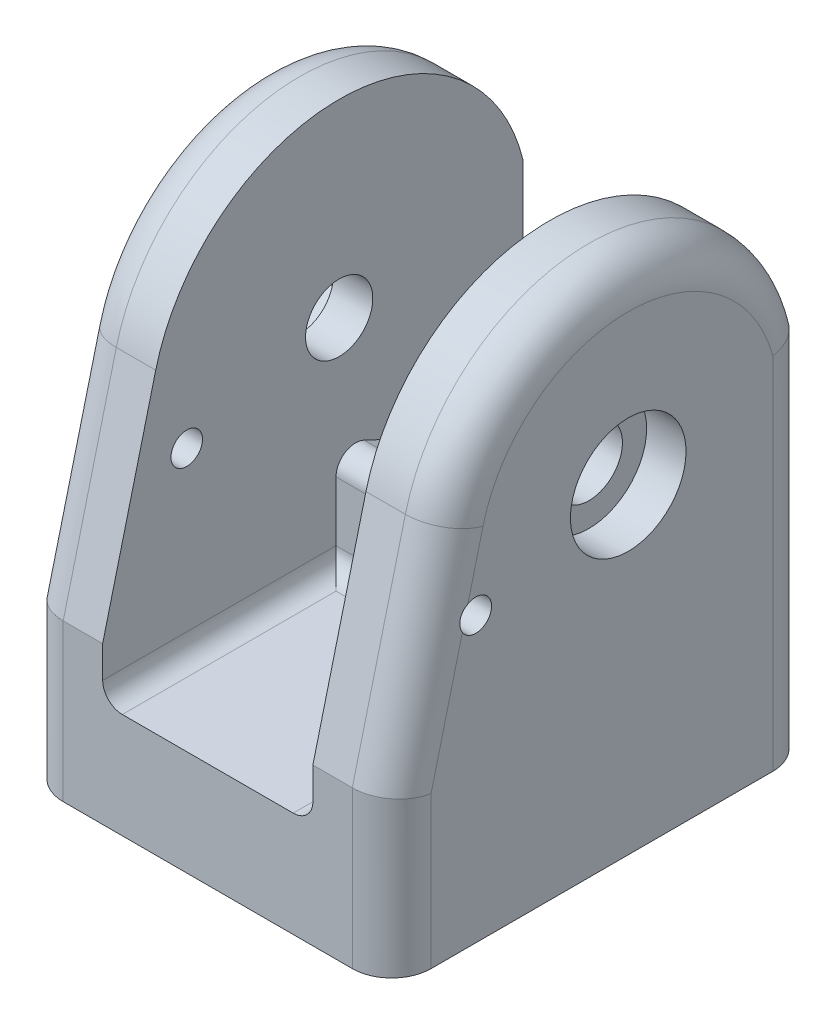
SolidWorks part; units mm, degrees
ref_plane "Front Plane" through (0, 0, 0) normal (0, 0, 1) x (1, 0, 0)
ref_plane "Top Plane" through (0, 0, 0) normal (0, 1, 0) x (1, 0, 0)
ref_plane "Right Plane" through (0, 0, 0) normal (1, 0, 0) x (0, 0, -1)
sketch "Sketch2" plane through (0, 0, 0) normal (0, 1, 0) x (1, 0, 0)
  line L0 (5, 10) -> (8.75, 10)
  line L1 (-8.75, -10) -> (8.75, -10)
  line L2 (-8.75, -10) -> (-8.75, 10)
  line L3 (-8.75, 10) -> (-5, 10)
  line L4 (8.75, -10) -> (8.75, 10)
  line L5 (-8.75, -10) -> (8.75, 10) construction
  line L6 (-8.75, 10) -> (8.75, -10) construction
  line L8 (-5, 10) -> (-5, 5)
  line L9 (-5, 5) -> (5, 5)
  line L10 (5, 10) -> (5, 5)
  point P0 (0, 0)
  point P6 (0, 0)
  point P8 (0, 0)
  point P15 (-5, 5)
  dimension "D1" = 17.5
  dimension "D2" = 20
  dimension "D3" = 3.75
  dimension "D4" = 5
extrude "Boss-Extrude1" add sketch "Sketch2" along normal blind 25
sketch "Sketch3" plane through (0, 25, 0) normal (0, 1, 0) x (1, 0, 0)
  line L0 (-8.75, -10) -> (8.75, -10) construction
  line L1 (-5, 10) -> (5, 10)
  line L2 (-5, 10) -> (-5, -10)
  line L3 (-5, -10) -> (5, -10)
  line L4 (5, 10) -> (5, -10)
  line L5 (5, 10) -> (5, 5) construction
extrude "Cut-Extrude1" cut sketch "Sketch3" against normal blind 20
sketch "Sketch4" plane through (8.75, 0, 0) normal (1, 0, 0) x (0, 0, -1)
  line L0 (10, 25) -> (10, 0) construction
  line L1 (-10, 25) -> (10, 25) construction
  line L2 (10, 17.3565) -> (10, 0)
  line L3 (10, 0) -> (-10, 0)
  line L4 (-10, 0) -> (-10, 7.4522)
  line L6 (-10, 7.4522) -> (-7.4764, 17.4522)
  line L7 (-10, 25) -> (-10, 0) construction
  circle A0 centre (1.25, 15.25) radius 1.6
  arc A1 (10, 17.3565) -> (-7.4764, 17.4522) centre (1.25, 15.25) ccw
  circle A2 centre (-6, 13.5) radius 0.75
  point P2 (0, 0)
  dimension "D1" = 8.75
  dimension "D4" = 3.2
  dimension "D7" = 9
  dimension "D6" = 1.75
  dimension "D8" = 1.5
  dimension "D2" = 9.75
  dimension "D3" = 10
  dimension "D5" = 4
extrude "Cut-Extrude2" cut sketch "Sketch4" against normal through all flip side to cut
fillet "Fillet1" radius 1.875 8 edges at (-8.75, 12.4522, 8.7382) (8.75, 12.4522, 8.7382) (-8.75, 8.6783, -10) (8.75, 8.6783, -10) (-8.75, 3.7261, 10) (8.75, 3.7261, 10) (-8.75, 24.2499, -1.2993) (8.75, 24.2499, -1.2993)
sketch "Sketch7" plane through (8.75, 0, 0) normal (1, 0, 0) x (0, 0, -1)
  line L1 (-10, 0) -> (10, 0)
  line L2 (-10, 0) -> (-10, 25)
  line L3 (-10, 25) -> (10, 25)
  line L4 (10, 0) -> (10, 25)
  dimension "D1" = 25
  dimension "D2" = 20
extrude "Cut-Extrude4" cut sketch "Sketch7" against normal blind 8.75
sketch "Sketch8" plane through (-5, 0, 0) normal (1, 0, 0) x (0, 0, -1)
  line L0 (5, 5) -> (5, 8.4)
  line L2 (5, 8.4) -> (1.1, 10.25)
  line L3 (1.1, 10.25) -> (1.1, 5)
  line L4 (5, 5) -> (-10, 5) construction
  line L5 (1.1, 5) -> (5, 5)
  line L7 (5, 5) -> (5, 0) construction
  point P10 (0, 0)
  point P13 (0, 0)
  point P14 (0, 0)
  dimension "D1" = 3.4
  dimension "D2" = 5.25
  dimension "D3" = 3.9
extrude "Boss-Extrude3" add sketch "Sketch8" along normal up to surface (5 mm away) up to face at (0, 2.5, 2.5)
fillet "Fillet2" radius 0.9375 4 edges at (-2.5, 8.4, -5) (-2.5, 10.25, -1.1) (-2.5, 5, -1.1) (-5, 5, 4.45)
mirror "Mirror2" about plane through (0, 0, 0) normal (-1, 0, 0) of bodies 108
sketch "Sketch11" plane through (8.75, 0, 0) normal (1, 0, 0) x (0, 0, -1)
  circle A0 centre (1.25, 15.25) radius 2.75
  dimension "D1" = 5.5
extrude "Cut-Extrude6" cut sketch "Sketch11" against normal blind 1.875
sketch "Sketch12" plane through (-8.75, 0, 0) normal (-1, 0, 0) x (0, 0, 1)
  line L1 (-1.25, 18.4254) -> (-4, 16.8377)
  line L2 (-4, 16.8377) -> (-4, 13.6623)
  line L3 (-4, 13.6623) -> (-1.25, 12.0746)
  line L4 (-1.25, 12.0746) -> (1.5, 13.6623)
  line L5 (1.5, 13.6623) -> (1.5, 16.8377)
  line L6 (1.5, 16.8377) -> (-1.25, 18.4254)
  circle A0 centre (-1.25, 15.25) radius 2.75 construction
  dimension "D1" = 5.5
extrude "Cut-Extrude7" cut sketch "Sketch12" against normal blind 1.875
